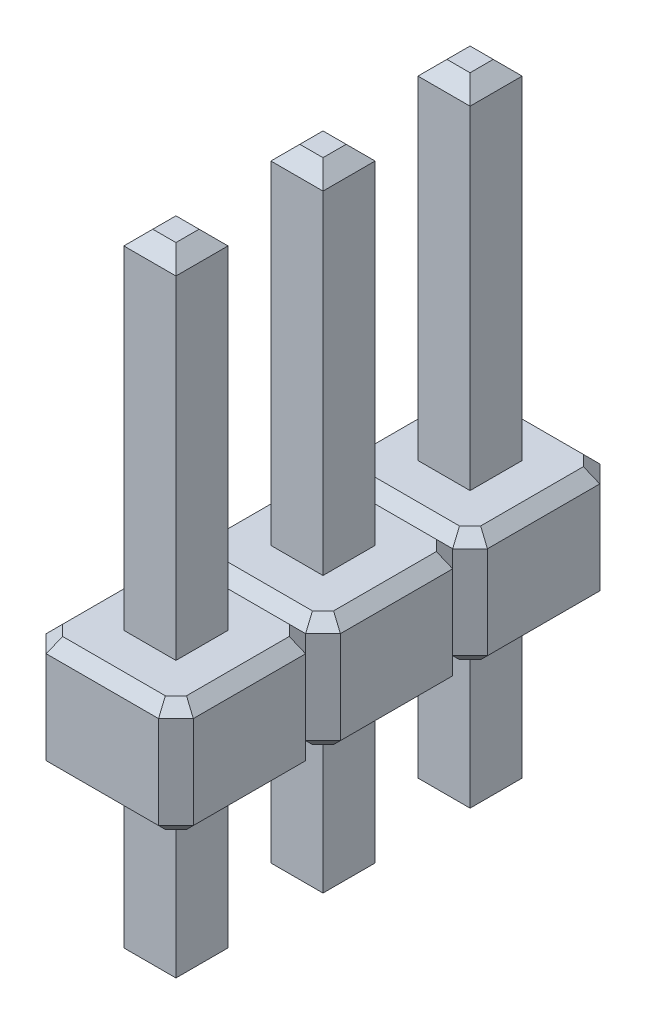
SolidWorks part; units mm, degrees
note: The reader was unsure of these and kept them because the rebuilt part matched: shared geometry of "Эскиз1<3>".
other "PIN5"
other "PIN3"
other "PIN1" parameters "D1"=27.9408, "D4"=1.6296, "D5"=1.1205, "D9"=0.3, "D10"=0.3, "D11"=0.3, "D12"=0.3, "D8"=0.5
ref_plane "Спереди" through (0, 0, 0) normal (0, 0, 1) x (1, 0, 0)
ref_plane "Сверху" through (0, 0, 0) normal (0, 1, 0) x (1, 0, 0)
ref_plane "Справа" through (0, 0, 0) normal (1, 0, 0) x (0, 0, -1)
sketch "Эскиз1" plane through (0, 0, 0) normal (0, 1, 0) x (1, 0, 0)
  line L1 (-0.45, -0.45) -> (0.45, -0.45)
  line L2 (-0.45, -0.45) -> (-0.45, 0.45)
  line L3 (-0.45, 0.45) -> (0.45, 0.45)
  line L4 (0.45, -0.45) -> (0.45, 0.45)
  line L5 (-0.45, -0.45) -> (0.45, 0.45) construction
  line L6 (-0.45, 0.45) -> (0.45, -0.45) construction
  line L26 (0.97, -1.27) -> (1.27, -0.97)
  line L27 (-0.97, -1.27) -> (0.97, -1.27)
  line L28 (-1.27, -0.97) -> (-1.27, 0.97)
  line L29 (-0.97, 1.27) -> (0.97, 1.27)
  line L30 (1.27, -0.97) -> (1.27, 0.97)
  line L31 (-1.27, -1.27) -> (1.27, 1.27) construction
  line L32 (-1.27, 1.27) -> (1.27, -1.27) construction
  line L33 (-0.97, -1.27) -> (-1.27, -0.97)
  line L34 (-1.27, 0.97) -> (-0.97, 1.27)
  line L35 (1.27, 0.97) -> (0.97, 1.27)
  circle A0 centre (0, 0) radius 0.45 construction
  dimension "D1" = 0.9
  dimension "D4" = 1.27
  dimension "D5" = 1.27
extrude "metal part" add sketch "Эскиз1" along normal blind 11 contours L1 L4 L3 L2
extrude "plastic part" add sketch "Эскиз1<3>" along direction (0, -1, 0) on the side of the normal blind 2 from offset 3 separate body contours L30 L35 L29 L34 L28 L33 L27 L26 L4 L1 L2 L3
sketch "Эскиз1<3>" plane through (0, 0, 0) normal (0, 1, 0) x (1, 0, 0) same geometry as "Эскиз1"
chamfer "Фаска1" distance 0.2 angle 45 16 edges at (1.12, 3, -1.12) (1.27, 3, 0) (1.12, 3, 1.12) (0, 3, 1.27) (-1.12, 3, 1.12) (-1.27, 3, 0) (-1.12, 3, -1.12) (0, 3, -1.27) (1.12, 5, -1.12) (0, 5, -1.27) (-1.12, 5, -1.12) (-1.27, 5, 0) (-1.12, 5, 1.12) (1.27, 5, 0) (1.12, 5, 1.12) (0, 5, 1.27) tangent propagation no
chamfer "Фаска2" distance 0.25 angle 45 8 edges at (0, 0, 0.45) (0.45, 0, 0) (0, 0, -0.45) (-0.45, 0, 0) (0.45, 11, 0) (0, 11, -0.45) (0, 11, 0.45) (-0.45, 11, 0)
pattern_linear "Линейный массив1" count 3 spacing 2.54 along (0, 0, -1) of bodies 103 104
combine bodies "Соединить2" operation type add bodies to combine 113 114 104
equation "\"D5@Эскиз1\"=\"D4@Эскиз1\""
